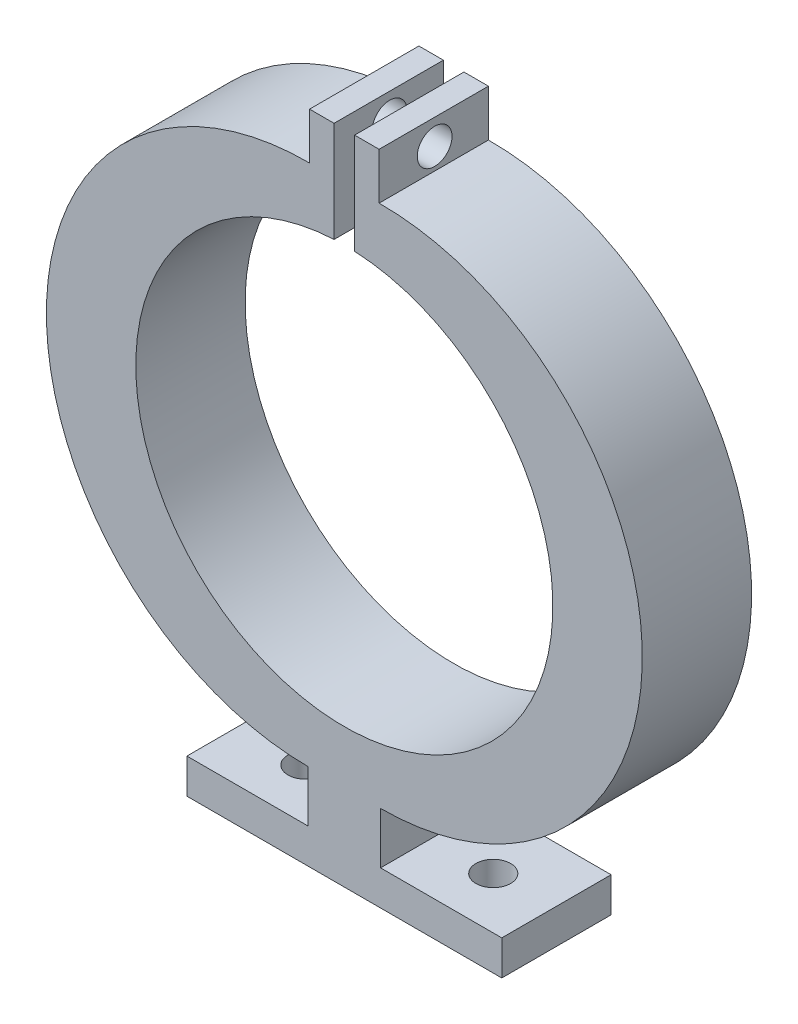
SolidWorks part; units mm, degrees
ref_plane "Front Plane" through (0, 0, 0) normal (0, 0, 1) x (1, 0, 0)
ref_plane "Top Plane" through (0, 0, 0) normal (0, 1, 0) x (1, 0, 0)
ref_plane "Right Plane" through (0, 0, 0) normal (1, 0, 0) x (0, 0, -1)
sketch "Sketch2" plane through (0, 0, 0) normal (0, 0, 1) x (1, 0, 0)
  line L0 (0, 42.9932) -> (0, -17.0437) construction
  line L1 (14.4009, -17.0437) -> (-14.4009, -17.0437)
  line L2 (-14.4009, -17.0437) -> (-14.4009, -13.8637)
  line L3 (-14.4009, -13.8637) -> (-3.3133, -13.8637)
  line L4 (-3.3133, -13.8637) -> (-3.3133, -9.1553)
  line L5 (-3.18, 38.7243) -> (-3.18, 42.9932)
  line L6 (-3.18, 42.9932) -> (3.18, 42.9932)
  line L7 (14.4009, -17.0437) -> (14.4009, -13.8637)
  line L8 (14.4009, -13.8637) -> (3.3133, -13.8637)
  line L9 (3.3133, -13.8637) -> (3.3133, -9.1553)
  line L10 (3.18, 38.7243) -> (3.18, 42.9932)
  arc A0 (-3.3133, -9.1553) -> (-3.18, 38.7243) centre (-3.3133, 14.7847) cw
  arc A1 (3.3133, -9.1553) -> (3.18, 38.7243) centre (3.3133, 14.7847) ccw
  point P0 (3.3133, -13.8637)
  dimension "D1" = 23.94
  dimension "D2" = 3.18
  dimension "D3" = 3.18
extrude "Boss-Extrude1" add sketch "Sketch2" along normal blind 10
sketch "Sketch3" plane through (0, 0, 10) normal (0, 0, 1) x (1, 0, 0)
  circle A0 centre (0, 14.7373) radius 19.075
  dimension "D1" = 38.15
extrude "Cut-Extrude1" cut sketch "Sketch3" against normal through all
sketch "Sketch4" plane through (0, 0, 10) normal (0, 0, 1) x (1, 0, 0)
  line L0 (3.18, 42.9932) -> (-3.18, 42.9932) construction
  line L1 (-0.9385, 42.9932) -> (0.9385, 42.9932)
  line L2 (-0.9385, 42.9932) -> (-0.9385, 33.7892)
  line L3 (-0.9385, 33.7892) -> (0.9385, 33.7892)
  line L4 (0.9385, 42.9932) -> (0.9385, 33.7892)
  line L5 (0, 0) -> (0, 12.768) construction
  circle A0 centre (0, 14.7373) radius 19.075 construction
extrude "Cut-Extrude2" cut sketch "Sketch4" against normal through all
sketch "Sketch5" plane through (3.18, 0, 0) normal (1, 0, 0) x (0, 0, -1)
  circle A0 centre (-4.9196, 40.6835) radius 1.59
  dimension "D1" = 3.18
extrude "Cut-Extrude3" cut sketch "Sketch5" against normal blind 10
sketch "Sketch6" plane through (0, -13.8637, 0) normal (0, 1, 0) x (1, 0, 0)
  circle A0 centre (8.9126, -5.2898) radius 1.59
  circle A1 centre (-8.2735, -5.2898) radius 1.59
  dimension "D1" = 3.18
  dimension "D2" = 3.18
extrude "Cut-Extrude4" cut sketch "Sketch6" against normal blind 10
